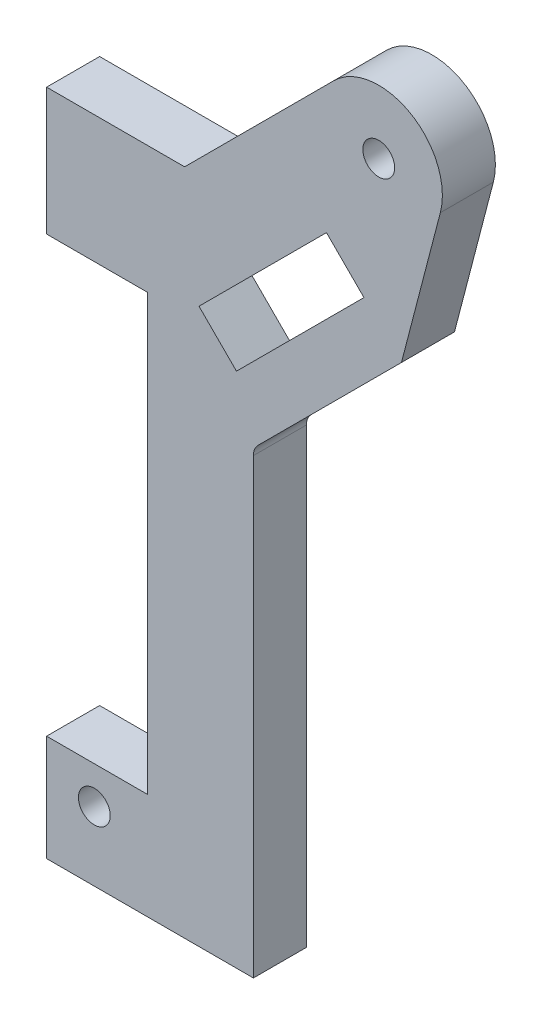
SolidWorks part; units mm, degrees
ref_plane "Plan de face" through (0, 0, 0) normal (0, 0, 1) x (1, 0, 0)
ref_plane "Plan de dessus" through (0, 0, 0) normal (0, 1, 0) x (1, 0, 0)
ref_plane "Plan de droite" through (0, 0, 0) normal (1, 0, 0) x (0, 0, -1)
sketch "Esquisse1" plane through (0, 0, 0) normal (0, 0, 1) x (1, 0, 0)
  line L0 (0, 10) -> (0, 0) construction
  line L1 (0, 0) -> (30, 0) construction
  line L2 (10, 10) -> (10, 51) construction
  line L3 (0, 63) -> (23.5147, 63) construction
  line L4 (36.8905, 64.3141) -> (24.8696, 52.2933)
  line L5 (9.5, 51) -> (0, 51) construction
  line L6 (36.8905, 64.3141) -> (40.426, 60.7786)
  line L7 (20, 10) -> (10.5, 10)
  line L8 (0, 30.5) -> (0, 10) construction
  line L9 (0, 30.5) -> (20, 30.5) construction
  line L10 (20, 10) -> (20, 51)
  line L11 (20, 51) -> (10.5, 51)
  line L12 (47.626, 71.307) -> (43.9615, 57.2431)
  line L13 (43.9615, 57.2431) -> (30, 43.2815)
  line L14 (24.8696, 52.2933) -> (28.4052, 48.7578)
  line L15 (28.4052, 48.7578) -> (40.426, 60.7786)
  line L16 (37.5772, 77.0624) -> (23.5147, 63)
  line L17 (10.5, 10) -> (10.5, 7)
  line L18 (9.5, 10) -> (0, 10) construction
  line L19 (9.5, 51) -> (9.5, 54) construction
  line L20 (9.5, 54) -> (10.5, 54) construction
  line L21 (10.5, 51) -> (10.5, 54)
  line L22 (9.5, 7) -> (10.5, 7) construction
  line L23 (9.5, 10) -> (9.5, 7) construction
  line L24 (30, 43.2815) -> (30, 0)
  line L25 (0, 63) -> (0, 51) construction
  line L26 (40.426, 60.7786) -> (43.9615, 57.2431) construction
  line L27 (10.5, 7) -> (10.5, 0)
  line L28 (10.5, 54) -> (10.5, 63)
  line L29 (23.5147, 63) -> (10.5, 63)
  line L30 (30, 0) -> (10.5, 0)
  circle A0 centre (5, 54.5) radius 1.5
  circle A1 centre (15, 54.5) radius 1.5 construction
  circle A2 centre (15, 6.5) radius 1.5
  circle A3 centre (5, 6.5) radius 1.5
  circle A4 centre (41.8198, 72.8198) radius 1.5
  circle A5 centre (41.8198, 72.8198) radius 1.725 construction
  arc A6 (37.5772, 77.0624) -> (47.626, 71.307) centre (41.8198, 72.8198) cw
  dimension "D6" = 20
  dimension "D8" = 5
  dimension "D11" = 3
  dimension "D16" = 10
  dimension "D5" = 3
  dimension "D12" = 17
  dimension "D13" = 6
  dimension "D1" = 41
  dimension "D2" = 12
  dimension "D3" = 3.5
  dimension "D4" = 5
  dimension "D7" = 5
  dimension "D9" = 1
  dimension "D10" = 3
  dimension "D14" = 10
extrude "Boss.-Extru.1" add sketch "Esquisse1" along normal blind 5 contours L3 L25 L1 L4 L14 L15 L23 L18 L8 L5 L19 L20 L21 L11 L10 L7 L17 L22 A0 A2 A3 region at (27.1223, 41.6192, 0)
fillet "Congé3" radius 1.5 1 edges at (30, 43.2815, 2.5)
